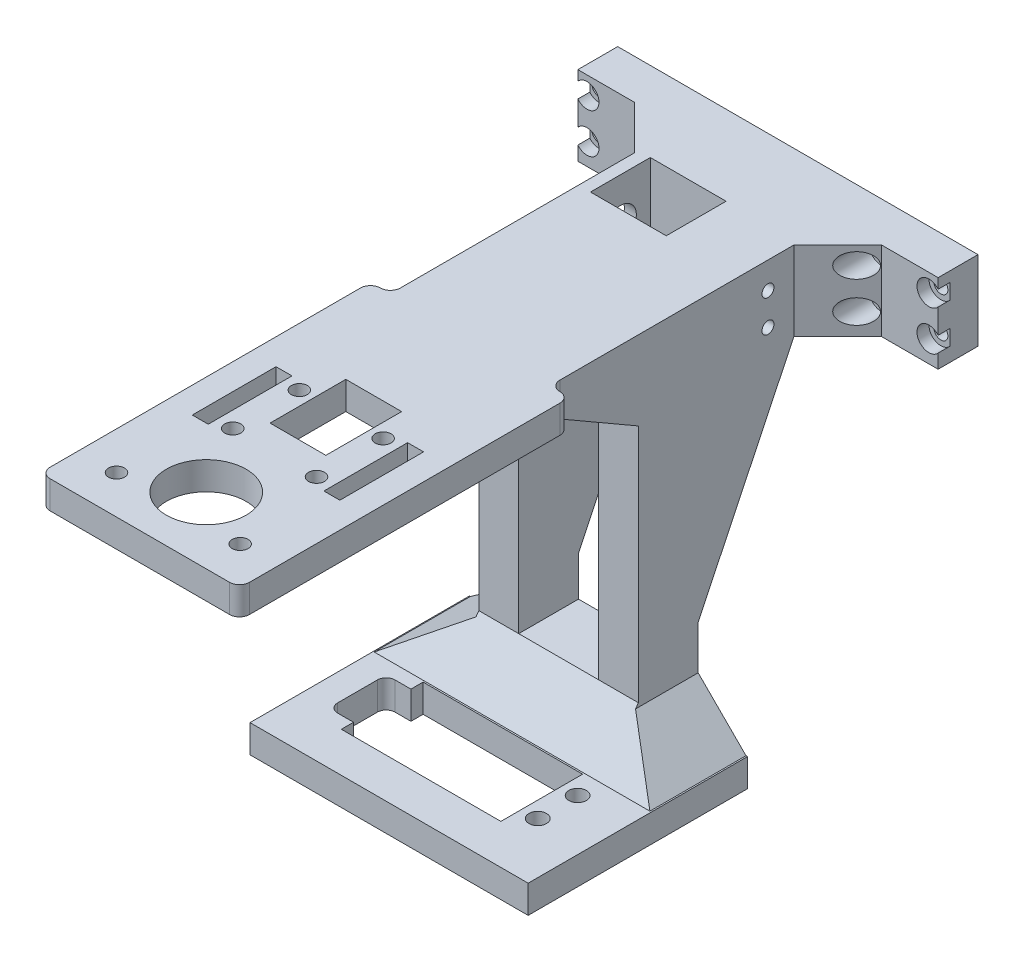
SolidWorks part; units mm, degrees
ref_plane "前视基准面" through (0, 0, 0) normal (0, 0, 1) x (1, 0, 0)
ref_plane "上视基准面" through (0, 0, 0) normal (0, 1, 0) x (1, 0, 0)
ref_plane "右视基准面" through (0, 0, 0) normal (1, 0, 0) x (0, 0, -1)
other "Configuration Table"
sketch "草图1" plane through (0, 0, 0) normal (0, 0, 1) x (1, 0, 0)
  line L0 (-42.87, 5.5) -> (-42.87, -4.5) construction
  line L1 (-45.17, 9.95) -> (45.17, 9.95)
  line L2 (-45.17, 9.95) -> (-45.17, -9.95)
  line L3 (-45.17, -9.95) -> (45.17, -9.95)
  line L4 (45.17, 9.95) -> (45.17, -9.95)
  line L5 (-45.17, 9.95) -> (45.17, -9.95) construction
  line L6 (-45.17, -9.95) -> (45.17, 9.95) construction
  line L7 (-42.87, -4.5) -> (-27.87, -4.5) construction
  line L8 (0, 0) -> (0, -9.95) construction
  line L9 (-27.87, -4.5) -> (-27.87, 5.5) construction
  line L10 (-42.87, 5.5) -> (-27.87, 5.5) construction
  circle A0 centre (-42.87, 5.5) radius 1.75
  circle A8 centre (-42.87, -4.5) radius 1.75
  circle A9 centre (-27.87, 5.5) radius 1.75
  circle A10 centre (-27.87, -4.5) radius 1.75
  circle A11 centre (27.87, -4.5) radius 1.75
  circle A12 centre (27.87, 5.5) radius 1.75
  circle A13 centre (42.87, -4.5) radius 1.75
  circle A14 centre (42.87, 5.5) radius 1.75
  point P0 (0, 0)
  dimension "D3" = 2.3
  dimension "D5" = 3.5
  dimension "D6" = 10
  dimension "D7" = 15
  dimension "D8" = 3.5
  dimension "D9" = 3.5
  dimension "D10" = 3.5
  dimension "D1" = 90.34
  dimension "D2" = 19.9
  dimension "D4" = 4.45
  dimension "D11" = 15
extrude "凸台-拉伸1" add sketch "草图1" along normal blind 10
sketch "草图2" plane through (0, 0, 10) normal (0, 0, 1) x (1, 0, 0)
  line L0 (-45.17, -9.95) -> (45.17, -9.95) construction
  line L1 (-20, 9.95) -> (20, 9.95)
  line L2 (-20, 9.95) -> (-20, -9.95)
  line L3 (-20, -9.95) -> (20, -9.95)
  line L4 (20, 9.95) -> (20, -9.95)
  line L5 (-20, 9.95) -> (20, -9.95) construction
  line L6 (-20, -9.95) -> (20, 9.95) construction
  point P0 (0, 0)
  dimension "D1" = 40
extrude "凸台-拉伸2" add sketch "草图2" along normal blind 50
sketch "草图3" plane through (0, -9.95, 0) normal (0, -1, 0) x (1, 0, 0)
  line L0 (20, 60) -> (20, 10) construction
  line L1 (-20, 60) -> (20, 60)
  line L2 (-20, 60) -> (-20, 45)
  line L3 (-20, 45) -> (20, 45)
  line L4 (20, 60) -> (20, 45)
  dimension "D1" = 15
extrude "凸台-拉伸3" add sketch "草图3" along normal blind 73
sketch "草图4" plane through (0, -82.95, 0) normal (0, -1, 0) x (1, 0, 0)
  line L12 (-32.37, 95) -> (32.37, 95)
  line L13 (-32.37, 95) -> (-32.37, 60)
  line L15 (32.37, 95) -> (32.37, 60)
  line L16 (-32.37, 95) -> (32.37, 60) construction
  line L17 (-32.37, 60) -> (32.37, 95) construction
  line L18 (-20, 45) -> (20, 45) construction
  line L19 (-32.37, 45) -> (32.37, 45)
  line L20 (-32.37, 45) -> (-32.37, 60)
  line L22 (32.37, 45) -> (32.37, 60)
  line L23 (-32.37, 45) -> (32.37, 60) construction
  line L24 (-32.37, 60) -> (32.37, 45) construction
  line L25 (-24.47, 79.75) -> (15.53, 79.75) construction
  line L26 (-24.47, 90) -> (15.53, 90)
  line L27 (-24.47, 90) -> (-24.47, 86.95)
  line L28 (-24.47, 69.5) -> (15.53, 69.5)
  line L29 (15.53, 90) -> (15.53, 69.5)
  line L30 (-4.47, 90) -> (-4.47, 69.5) construction
  line L31 (-24.47, 72.55) -> (-24.47, 69.5)
  line L35 (-24.47, 86.95) -> (-24.47, 72.55) construction
  line L36 (-24.47, 86.95) -> (-28.47, 86.95)
  line L37 (-30.67, 84.75) -> (-30.67, 74.75)
  line L38 (-28.47, 72.55) -> (-24.47, 72.55)
  circle A0 centre (19.53, 84.75) radius 2.2
  circle A4 centre (19.53, 74.75) radius 2.2
  arc A5 (-30.67, 74.75) -> (-28.47, 72.55) centre (-28.47, 74.75) ccw
  arc A6 (-30.67, 84.75) -> (-28.47, 86.95) centre (-28.47, 84.75) cw
  point P2 (0, 77.5)
  point P11 (0, 52.5)
  dimension "D7" = 4
  dimension "D11" = 4.4
  dimension "D2" = 64.74
  dimension "D3" = 35
  dimension "D4" = 15
  dimension "D5" = 40
  dimension "D1" = 15
  dimension "D6" = 20.5
  dimension "D8" = 5.25
  dimension "D9" = 7.9
  dimension "D10" = 5
extrude "凸台-拉伸4" add sketch "草图4" along normal blind 7
sketch "草图15" plane through (0, 0, 10) normal (0, 0, 1) x (1, 0, 0)
  circle A0 centre (-42.87, 5.5) radius 3
  circle A1 centre (-42.87, -4.5) radius 3
  circle A2 centre (-27.87, 5.5) radius 3
  circle A3 centre (-27.87, -4.5) radius 3
  circle A4 centre (27.87, 5.5) radius 3
  circle A5 centre (27.87, -4.5) radius 3
  circle A6 centre (42.87, 5.5) radius 3
  circle A7 centre (42.87, -4.5) radius 3
  dimension "D1" = 6
  dimension "D2" = 6
  dimension "D3" = 6
  dimension "D4" = 6
  dimension "D5" = 6
  dimension "D6" = 6
  dimension "D7" = 6
  dimension "D8" = 6
extrude "切除-拉伸5" cut sketch "草图15" against normal blind 3
sketch "草图16" plane through (-20, 0, 0) normal (-1, 0, 0) x (0, 0, 1)
  line L21 (60, 9.95) -> (60, -82.95) construction
  line L22 (45, -9.95) -> (60, -9.95)
  line L23 (45, -9.95) -> (45, -69.95)
  line L24 (45, -69.95) -> (60, -69.95)
  line L25 (60, -9.95) -> (60, -69.95)
  dimension "D2" = 60
extrude "切除-拉伸6" cut sketch "草图16" against normal blind 20 from offset 10 offset against normal yes
chamfer "倒角3" distance 13 angle 35 1 edges at (0, -82.95, 60)
chamfer "倒角1" distance 11 angle 45 2 edges at (20, 0, 10) (-20, 0, 10)
sketch "草图22" plane through (0, 0, 60) normal (0, 0, 1) x (1, 0, 0)
  line L0 (20, -9.95) -> (20, 9.95) construction
  line L1 (-20, 9.95) -> (20, 9.95)
  line L2 (-20, 9.95) -> (-20, 2.95)
  line L3 (-20, 2.95) -> (20, 2.95)
  line L4 (20, 9.95) -> (20, 2.95)
  dimension "D1" = 7
extrude "凸台-拉伸7" add sketch "草图22" along normal blind 105
sketch "草图23" plane through (0, 9.95, 0) normal (0, 1, 0) x (1, 0, 0)
  line L0 (0, -45) -> (0, -165) construction
  line L1 (10, -45) -> (-10, -45) construction
  line L2 (20, -165) -> (-20, -165) construction
  line L3 (2.5789, -112.35) -> (18.5, -112.35) construction
  line L4 (-18.5, -112.35) -> (-7, -112.35) construction
  line L5 (-18.5, -112.35) -> (-18.5, -158.35) construction
  line L6 (-18.5, -158.35) -> (18.5, -158.35) construction
  line L7 (18.5, -112.35) -> (18.5, -158.35) construction
  line L8 (-18.5, -112.35) -> (18.5, -158.35) construction
  line L9 (-18.5, -158.35) -> (18.5, -112.35) construction
  line L10 (18.5, -133.35) -> (14.5, -133.35)
  line L11 (-18.5, -112.35) -> (-14.5, -112.35)
  line L12 (-18.5, -112.35) -> (-18.5, -133.35)
  line L13 (-18.5, -133.35) -> (-14.5, -133.35)
  line L14 (-14.5, -112.35) -> (-14.5, -133.35)
  line L15 (-10, -138.35) -> (10, -138.35) construction
  line L16 (-10, -138.35) -> (-10, -158.35) construction
  line L17 (-10, -158.35) -> (10, -158.35) construction
  line L18 (10, -138.35) -> (10, -158.35) construction
  line L19 (-10, -138.35) -> (10, -158.35) construction
  line L20 (-10, -158.35) -> (10, -138.35) construction
  line L21 (14.5, -112.35) -> (14.5, -133.35)
  line L22 (18.5, -112.35) -> (14.5, -112.35)
  line L23 (18.5, -112.35) -> (18.5, -133.35)
  line L24 (-20, -60) -> (-10, -60) construction
  line L25 (14.5, -122.85) -> (-14.5, -122.85) construction
  line L26 (-7, -106.35) -> (7, -106.35)
  line L31 (-7, -106.35) -> (-7, -125.35)
  line L32 (-7, -125.35) -> (7, -125.35)
  line L33 (7, -106.35) -> (7, -125.35)
  line L34 (-7, -106.35) -> (7, -125.35) construction
  line L35 (-7, -125.35) -> (7, -106.35) construction
  circle A0 centre (15.5, -155.35) radius 2
  circle A1 centre (-15.5, -155.35) radius 2
  circle A2 centre (10.5, -114.5) radius 2
  circle A3 centre (-10.5, -114.5) radius 2
  circle A4 centre (-10.5, -131.2) radius 2
  circle A5 centre (10.5, -131.2) radius 2
  circle A6 centre (0, -148.35) radius 10
  point P6 (0, -135.35)
  point P16 (0, -148.35)
  point P38 (0, -115.85)
  dimension "D5" = 3
  dimension "D7" = 4
  dimension "D11" = 4
  dimension "D13" = 4
  dimension "D17" = 5
  dimension "D2" = 37
  dimension "D3" = 4
  dimension "D4" = 21
  dimension "D6" = 3
  dimension "D8" = 20
  dimension "D9" = 20
  dimension "D10" = 88.35
  dimension "D12" = 2.15
  dimension "D14" = 14
  dimension "D15" = 19
  dimension "D16" = 6
extrude "切除-拉伸9" cut sketch "草图23" against normal blind 7 contours L14 L4 L5 L13 | L4 L21 L10 L7 | A1 | A0 | L18 L15 L16 L6 | L31 L26 L33 L32 | A3 | A2 | A4 | A5 | A6
chamfer "倒角4" distance 12.8 angle 60 1 edges at (-15, 2.95, 60)
sketch "草图25" plane through (20, 0, 0) normal (1, 0, 0) x (0, 0, -1)
  line L5 (-165, 9.95) -> (-82.1703, 9.95)
  line L6 (-165, 9.95) -> (-165, 2.95)
  line L7 (-165, 2.95) -> (-82.1703, 2.95)
  line L8 (-82.1703, 9.95) -> (-82.1703, 2.95)
extrude "凸台-拉伸8" add sketch "草图25" along normal blind 5
sketch "草图26" plane through (-20, 0, 0) normal (-1, 0, 0) x (0, 0, 1)
  line L1 (165, 9.95) -> (82.1703, 9.95)
  line L2 (165, 9.95) -> (165, 2.95)
  line L3 (165, 2.95) -> (82.1703, 2.95)
  line L4 (82.1703, 9.95) -> (82.1703, 2.95)
extrude "凸台-拉伸9" add sketch "草图26" along normal blind 5
sketch "草图28" plane through (0, -89.95, 0) normal (0, -1, 0) x (1, 0, 0)
  line L1 (32.37, 95) -> (-32.37, 95)
  line L2 (32.37, 95) -> (32.37, 100)
  line L3 (32.37, 100) -> (-32.37, 100)
  line L4 (-32.37, 95) -> (-32.37, 100)
  dimension "D1" = 5
extrude "凸台-拉伸10" add sketch "草图28" against normal blind 7
sketch "草图31" plane through (-10, 0, 0) normal (1, 0, 0) x (0, 0, -1)
  line L0 (-45, -9.95) -> (-21, -9.95) construction
  line L1 (-60, 9.95) -> (-35, 9.95)
  line L2 (-60, 9.95) -> (-60, -9.95)
  line L3 (-60, -9.95) -> (-35, -9.95)
  line L4 (-35, 9.95) -> (-35, -9.95)
  line L5 (-10, -9.95) -> (-45, -9.95) construction
  line L6 (-10, 9.95) -> (-20, 9.95)
  line L7 (-10, 9.95) -> (-10, -9.95)
  line L8 (-10, -9.95) -> (-20, -9.95)
  line L9 (-20, 9.95) -> (-20, -9.95)
  dimension "D1" = 25
  dimension "D2" = 10
extrude "凸台-拉伸12" add sketch "草图31" along normal blind 20
sketch "草图32" plane through (-10, 0, 0) normal (1, 0, 0) x (0, 0, -1)
  line L0 (-27.5, 9.95) -> (-27.5, -9.95) construction
  line L1 (-35, 9.95) -> (-20, 9.95) construction
  line L2 (-20, -9.95) -> (-35, -9.95) construction
  circle A0 centre (-27.5, 3.2807) radius 1.5
  circle A1 centre (-27.5, -4.7193) radius 1.5
  dimension "D1" = 8
  dimension "D2" = 3
  dimension "D3" = 3
sketch "草图33" plane through (-20, 0, 0) normal (-1, 0, 0) x (0, 0, 1)
  line L0 (27.5, -9.95) -> (27.5, 9.95) construction
  line L1 (45, -9.95) -> (21, -9.95) construction
  line L2 (82.1703, 9.95) -> (21, 9.95) construction
  circle A2 centre (27.5, -0.7193) radius 4
  dimension "D1" = 8
extrude "切除-拉伸11" cut sketch "草图33" against normal blind 10
extrude "切除-拉伸12" cut sketch "草图32" along normal blind 30
sketch "草图35" plane through (-20, 0, 0) normal (-1, 0, 0) x (0, 0, 1)
  line L0 (21, -9.95) -> (45, -59.95)
  line L1 (45, -9.95) -> (21, -9.95) construction
  line L2 (45, -82.95) -> (45, -9.95) construction
  line L3 (45, -59.95) -> (45, -9.95)
  line L4 (45, -9.95) -> (21, -9.95)
  dimension "D1" = 24
  dimension "D2" = 50
extrude "凸台-拉伸13" add sketch "草图35" against normal blind 10
sketch "草图36" plane through (20, 0, 0) normal (1, 0, 0) x (0, 0, -1)
  line L1 (-21, -9.95) -> (-45, -9.95)
  line L2 (-45, -9.95) -> (-45, -59.95)
  line L3 (-45, -59.95) -> (-21, -9.95)
  line L9 (-35, -9.95) -> (-60, -9.95)
  line L10 (-60, -9.95) -> (-60, -69.95)
  line L11 (-60, -69.95) -> (-45, -69.95)
  line L12 (-45, -69.95) -> (-45, -59.95)
  line L13 (-45, -59.95) -> (-21, -9.95)
  line L14 (-21, -9.95) -> (-20, -9.95)
  line L15 (-20, -9.95) -> (-20, 9.95)
  line L16 (-20, 9.95) -> (-35, 9.95)
  line L17 (-35, 9.95) -> (-35, -9.95)
  line L21 (-45, -69.95) -> (-45, -59.95)
  line L25 (-20, 9.95) -> (-35, 9.95)
  line M18 (-45, -82.95) -> (-45, -9.95)
  line M19 (-45, -9.95) -> (-21, -9.95)
  dimension "D1" = 0
extrude "凸台-拉伸14" add sketch "草图36" against normal blind 10 contours L3 M18 M19
fillet "圆角2" radius 2.5 4 edges at (-25, 6.45, 82.1703) (25, 6.45, 82.1703) (20, 6.45, 82.1703) (-20, 6.45, 82.1703)
fillet "圆角3" radius 2.5 2 edges at (25, 6.45, 165) (-25, 6.45, 165)
sketch "草图37" plane through (-10, 0, 0) normal (1, 0, 0) x (0, 0, -1)
  line L3 (-60, -9.85) -> (-60, 2.95)
  line L4 (-60, 2.95) -> (-82.1703, 2.95)
  line L5 (-82.1703, 2.95) -> (-60, -9.85)
  line L6 (-60, -9.85) -> (-60, 2.95)
  line L7 (-60, 2.95) -> (-82.1703, 2.95)
  line L8 (-82.1703, 2.95) -> (-60, -9.85)
  dimension "D1" = 0
extrude "凸台-拉伸15" add sketch "草图37" along normal blind 10 from offset 20
sketch "草图38" plane through (-32.37, 0, 0) normal (-1, 0, 0) x (0, 0, 1)
  line L4 (100, -82.95) -> (45, -82.95)
  line L5 (45, -82.95) -> (45, -89.95)
  line L6 (45, -89.95) -> (100, -89.95)
  line L7 (100, -89.95) -> (100, -82.95)
  line L8 (100, -82.95) -> (45, -82.95)
  line L9 (45, -82.95) -> (45, -89.95)
  line L10 (45, -89.95) -> (100, -89.95)
  line L11 (100, -89.95) -> (100, -82.95)
  dimension "D1" = 0
extrude "凸台-拉伸16" add sketch "草图38" along normal blind 5
chamfer "倒角5" distance 12 angle 55 1 edges at (-20, -82.95, 57.0513)
chamfer "倒角6" distance 12 angle 45 1 edges at (20, -82.95, 57.0513)
sketch "草图39" plane through (10, 0, 0) normal (-1, 0, 0) x (0, 0, 1)
  line L0 (20, 9.95) -> (35, 9.95)
  line L1 (35, 9.95) -> (35, -9.95)
  line L2 (35, -9.95) -> (20, -9.95)
  line L3 (20, -9.95) -> (20, 9.95)
  circle A0 centre (27.5, 3.2807) radius 1.5
  circle A1 centre (27.5, -4.7193) radius 1.5
extrude "凸台-拉伸17" add sketch "草图39" along normal blind 3
sketch "草图40" plane through (-10, 0, 0) normal (1, 0, 0) x (0, 0, -1)
  line L0 (-35, 9.95) -> (-20, 9.95)
  line L1 (-20, 9.95) -> (-20, -9.95)
  line L2 (-20, -9.95) -> (-35, -9.95)
  line L3 (-35, -9.95) -> (-35, 9.95)
  circle A0 centre (-27.5, -0.7193) radius 4
extrude "凸台-拉伸18" add sketch "草图40" along normal blind 3
sketch "草图41" plane through (0, 9.95, 0) normal (0, 1, 0) x (1, 0, 0)
  line L0 (-7, -20) -> (-17, -20)
  line L1 (-7, -20) -> (-7, -35)
  line L2 (-7, -35) -> (-17, -35)
  line L3 (-17, -35) -> (-17, -20)
  dimension "D1" = 10
extrude "切除-拉伸13" cut sketch "草图41" against normal blind 60
sketch "草图42" plane through (7, 0, 0) normal (-1, 0, 0) x (0, 0, 1)
  line L4 (20, 9.95) -> (20, -9.95)
  line L5 (20, -9.95) -> (35, -9.95)
  line L6 (35, -9.95) -> (35, 9.95)
  line L7 (35, 9.95) -> (20, 9.95)
  line L8 (20, 9.95) -> (20, -9.95)
  line L9 (20, -9.95) -> (35, -9.95)
  line L10 (35, -9.95) -> (35, 9.95)
  line L11 (35, 9.95) -> (20, 9.95)
  circle A0 centre (27.5, 3.2807) radius 3.5
  circle A1 centre (27.5, -4.7193) radius 3.5
  dimension "D2" = 7
  dimension "D3" = 7
  dimension "D1" = 0
extrude "凸台-拉伸20" add sketch "草图42" along normal blind 5
equation "\"、\"=80"
